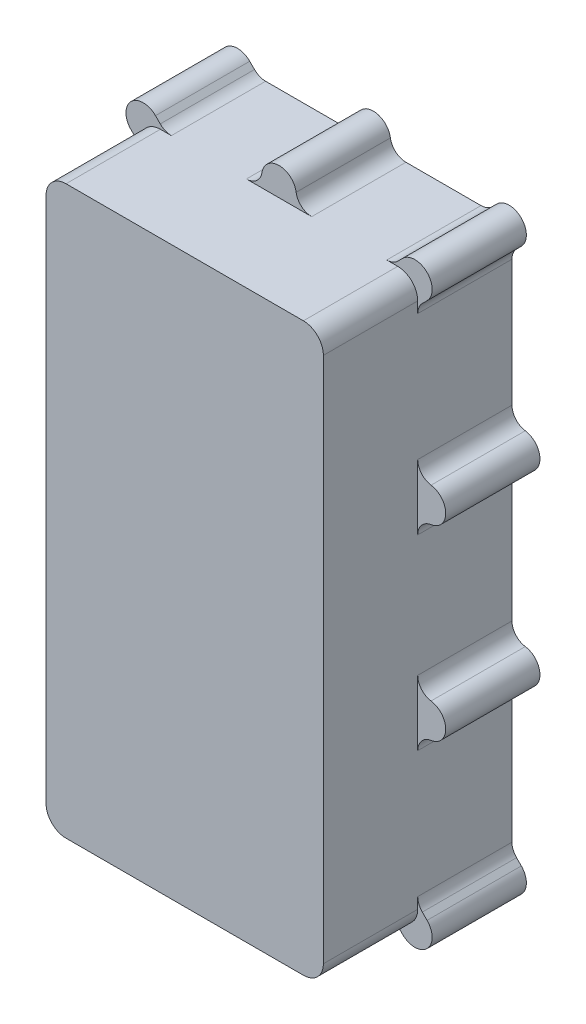
SolidWorks part; units mm, degrees
material "ABS"
ref_plane "X-Y Datum" through (0, 0, 0) normal (0, 0, 1) x (1, 0, 0)
ref_plane "X-Z Datum" through (0, 0, 0) normal (0, 1, 0) x (1, 0, 0)
ref_plane "Y-Z Datum" through (0, 0, 0) normal (1, 0, 0) x (0, 0, -1)
sketch "Sketch1" plane through (0, 0, 0) normal (0, 0, 1) x (1, 0, 0)
  line L0 (1.8162, 48.1563) -> (125.4513, 48.1563) construction
  line L1 (24.3593, 48.1563) -> (24.3593, 120.2923) construction
  line L3 (24.3593, 120.2923) -> (125.4513, 120.2923) construction
  line L8 (125.4513, 48.1563) -> (125.4513, 120.2923) construction
  line L33 (24.3593, 120.2923) -> (1.8162, 120.2923) construction
  line L34 (24.3593, 120.2923) -> (24.3593, 48.1563) construction
  line L35 (63.6337, 48.1563) -> (63.6337, 43.0763) construction
  line L36 (1.8162, 120.2923) -> (1.8162, 48.1563) construction
  line L41 (24.3593, 120.2923) -> (23.7243, 120.2923) construction
  line L42 (24.3593, 120.2923) -> (24.3593, 122.8323) construction
  line L44 (27.5343, 14.7553) -> (27.5343, 43.0763) construction
  line L45 (125.4513, 120.2923) -> (127.9913, 120.2923) construction
  line L46 (27.5343, 14.7553) -> (125.4513, 14.7553) construction
  line L47 (23.7243, 122.8323) -> (127.9913, 122.8323)
  line L48 (23.7243, 122.8323) -> (23.7243, -21.9477)
  line L49 (23.7243, -21.9477) -> (127.9913, -21.9477)
  line L50 (127.9913, 122.8323) -> (127.9913, -21.9477)
  line L51 (125.4513, 14.7553) -> (125.4513, 43.0763) construction
  line L52 (27.5343, 43.0763) -> (125.4513, 43.0763) construction
  line L53 (23.7243, 120.2923) -> (23.7243, 48.1563) construction
  circle A17 centre (30.4553, 114.1963) radius 2.1 construction
  circle A18 centre (119.8633, 115.2123) radius 2.1 construction
  circle A19 centre (119.6813, 54.2533) radius 2.1 construction
  circle A20 centre (29.4393, 53.2363) radius 2.1 construction
  circle A26 centre (31.9793, 18.4383) radius 2.1 construction
  circle A27 centre (31.9793, 39.3933) radius 2.1 construction
  circle A28 centre (120.6193, 28.8183) radius 2.1 construction
sketch "Sketch2" plane through (0, 0, 0) normal (0, 0, 1) x (1, 0, 0)
  line L4 (55.176, 122.8323) -> (127.9913, 122.8323)
  line L6 (55.176, 48.5244) -> (55.176, 50.9244) construction
  line L7 (55.176, -21.05) -> (127.9913, -21.05)
  line L8 (127.9913, 122.8323) -> (127.9913, -21.05)
  line L9 (55.176, 110.2103) -> (127.9913, -21.05) construction
  line L10 (55.176, -8.428) -> (127.9913, 122.8323) construction
  line L11 (55.176, 50.9244) -> (55.176, -21.05)
  line L12 (55.176, 50.9244) -> (55.176, 122.8323)
  circle A7 centre (88.0827, 6.45) radius 27.5
  circle A8 centre (88.0294, 95.3501) radius 27.5
  circle A9 centre (98.216, 50.8911) radius 6.477
  circle A10 centre (77.896, 50.9089) radius 6.477
  circle A11 centre (121.5143, 31.8208) radius 6.477
  circle A12 centre (115.996, 50.8756) radius 2.4
  circle A13 centre (55.176, 50.9244) radius 2.4
  point P14 (88.0827, 50.8911)
sketch "Sketch3" plane through (0, 0, 0) normal (0, 0, 1) x (1, 0, 0)
  line L7 (0, 0) -> (76.2, 0)
  line L10 (0, 0) -> (0, 168.275)
  line L11 (0, 168.275) -> (76.2, 168.275)
  line L12 (76.2, 0) -> (76.2, 168.275)
  dimension "D1" = 168.275
  dimension "D2" = 76.2
extrude "Boss-Extrude1" add sketch "Sketch3" along normal blind 53.975
shell "Shell1" thickness 6 removed face at (38.1, 84.1375, 0) outward yes
fillet "Fillet1" radius 5.334 4 edges at (76.2, 168.275, 26.9875) (76.2, 0, 26.9875) (0, 0, 26.9875) (0, 168.275, 26.9875)
fillet "Fillet2" radius 6.35 4 edges at (-6, -6, 29.9875) (-6, 174.275, 29.9875) (82.2, 174.275, 29.9875) (82.2, -6, 29.9875)
sketch "Sketch6" plane through (0, 0, 0) normal (0, 0, -1) x (-1, 0, 0)
  line L8 (-5.334, 172.5577) -> (-70.866, 172.5577)
  line L9 (-80.4827, 162.941) -> (-80.4827, 5.334)
  line L10 (-70.866, -4.2827) -> (-5.334, -4.2827)
  line L11 (4.2827, 5.334) -> (4.2827, 162.941)
  line L12 (-79.2, 162.941) -> (-79.2, 5.334)
  line L13 (-70.866, -3) -> (-5.334, -3)
  line L14 (3, 5.334) -> (3, 162.941)
  line L15 (-5.334, 171.275) -> (-70.866, 171.275)
  line L16 (-79.2, 162.941) -> (-79.2, 5.334) construction
  line L17 (-70.866, -3) -> (-5.334, -3) construction
  line L18 (3, 5.334) -> (3, 162.941) construction
  line L19 (-5.334, 171.275) -> (-70.866, 171.275) construction
  line L20 (-77.9173, 162.941) -> (-77.9173, 5.334)
  line L21 (-70.866, -1.7173) -> (-5.334, -1.7173)
  line L22 (1.7173, 5.334) -> (1.7173, 162.941)
  line L23 (-5.334, 169.9923) -> (-70.866, 169.9923)
  arc A8 (-70.866, 172.5577) -> (-80.4827, 162.941) centre (-70.866, 162.941) ccw
  arc A9 (-80.4827, 5.334) -> (-70.866, -4.2827) centre (-70.866, 5.334) ccw
  arc A10 (-5.334, -4.2827) -> (4.2827, 5.334) centre (-5.334, 5.334) ccw
  arc A11 (4.2827, 162.941) -> (-5.334, 172.5577) centre (-5.334, 162.941) ccw
  arc A12 (-70.866, 171.275) -> (-79.2, 162.941) centre (-70.866, 162.941) ccw
  arc A13 (-79.2, 5.334) -> (-70.866, -3) centre (-70.866, 5.334) ccw
  arc A14 (-5.334, -3) -> (3, 5.334) centre (-5.334, 5.334) ccw
  arc A15 (3, 162.941) -> (-5.334, 171.275) centre (-5.334, 162.941) ccw
  arc A16 (-70.866, 171.275) -> (-79.2, 162.941) centre (-70.866, 162.941) ccw construction
  arc A17 (-79.2, 5.334) -> (-70.866, -3) centre (-70.866, 5.334) ccw construction
  arc A18 (-5.334, -3) -> (3, 5.334) centre (-5.334, 5.334) ccw construction
  arc A19 (3, 162.941) -> (-5.334, 171.275) centre (-5.334, 162.941) ccw construction
  arc A20 (-77.9173, 5.334) -> (-70.866, -1.7173) centre (-70.866, 5.334) ccw
  arc A21 (-5.334, -1.7173) -> (1.7173, 5.334) centre (-5.334, 5.334) ccw
  arc A22 (1.7173, 162.941) -> (-5.334, 169.9923) centre (-5.334, 162.941) ccw
  arc A23 (-70.866, 169.9923) -> (-77.9173, 162.941) centre (-70.866, 162.941) ccw
  dimension "D4" = 7.0513
  dimension "D5" = 2.5654
  dimension "D1" = 3
  dimension "D2" = 1.2827
  dimension "D3" = 1.2827
extrude "Cut-Extrude1" cut sketch "Sketch6" against normal blind 1.2446
fillet "Fillet3" radius 0.254 16 edges at (-4.2827, 84.1375, 1.2446) (-1.466, -1.466, 1.2446) (38.1, -4.2827, 1.2446) (77.666, -1.466, 1.2446) (80.4827, 84.1375, 1.2446) (77.666, 169.741, 1.2446) (38.1, 172.5577, 1.2446) (-1.466, 169.741, 1.2446) (75.852, 167.927, 1.2446) (77.9173, 84.1375, 1.2446) (75.852, 0.348, 1.2446) (38.1, -1.7173, 1.2446) (0.348, 0.348, 1.2446) (-1.7173, 84.1375, 1.2446) (0.348, 167.927, 1.2446) (38.1, 169.9923, 1.2446)
fillet "Fillet4" radius 0.127 16 edges at (75.852, 167.927, 0) (38.1, 169.9923, 0) (0.348, 167.927, 0) (-1.7173, 84.1375, 0) (0.348, 0.348, 0) (38.1, -1.7173, 0) (75.852, 0.348, 0) (77.666, 169.741, 0) (38.1, 172.5577, 0) (-1.466, 169.741, 0) (-4.2827, 84.1375, 0) (-1.466, -1.466, 0) (38.1, -4.2827, 0) (77.666, -1.466, 0) (77.9173, 84.1375, 0) (80.4827, 84.1375, 0)
sketch "Sketch7" plane through (0, 0, 53.975) normal (0, 0, -1) x (-1, 0, 0)
  line L0 (-76.2, 32) -> (0, 32)
  line L1 (-76.2, 5.334) -> (-76.2, 162.941) construction
  line L2 (0, 162.941) -> (0, 5.334) construction
  line L3 (-76.2, 34.5) -> (0, 34.5)
  line L4 (-5.334, 0) -> (-70.866, 0) construction
  line L5 (-76.2, 32) -> (-76.2, 34.5)
  line L6 (0, 32) -> (0, 34.5)
  dimension "D2" = 32
  dimension "D1" = 2.5
extrude "Boss-Extrude2" add sketch "Sketch7" along normal up to surface (53.975 mm away) up to face at (38.1, 84.1375, 0)
sketch "Sketch8" plane through (0, 0, 0) normal (0, 0, -1) x (-1, 0, 0)
  line L0 (-5.334, 5.334) -> (5.0914, -5.0914)
  line L1 (-1.7782, -6) -> (1.2023, -8.9805)
  line L2 (-0.35, -6) -> (-75.85, -6) construction
  line L3 (-5.334, -4.2827) -> (-5.334, -4.4097)
  line L4 (4.4097, 5.334) -> (4.2827, 5.334)
  line L5 (-5.334, -4.2827) -> (-5.334, -4.4097)
  line L6 (4.4097, 5.334) -> (4.2827, 5.334)
  line L7 (6, 1.7782) -> (8.9805, -1.2023)
  line L8 (6, 167.925) -> (6, 0.35) construction
  line L9 (-38.1, -6) -> (-38.1, 174.275) construction
  line L10 (-75.85, 174.275) -> (-0.35, 174.275) construction
  line L11 (-82.2, 84.1375) -> (6, 84.1375) construction
  line L12 (-82.2, 0.35) -> (-82.2, 167.925) construction
  circle A0 centre (5.0914, -5.0914) radius 3.025
  circle A1 centre (5.0914, -5.0914) radius 5.5
  arc A3 (-5.334, -4.4097) -> (4.4097, 5.334) centre (-5.334, 5.334) ccw
  arc A4 (-5.334, -4.2827) -> (4.2827, 5.334) centre (-5.334, 5.334) ccw
  arc A5 (-5.334, -4.4097) -> (4.4097, 5.334) centre (-5.334, 5.334) ccw
  arc A6 (-5.334, -4.2827) -> (4.2827, 5.334) centre (-5.334, 5.334) ccw
  point P6 (1.5558, -1.5558)
  dimension "D1" = 6.05
  dimension "D4" = 11
  dimension "D3" = 5
  dimension "D2" = 0
extrude "Boss-Extrude3" add sketch "Sketch8" against normal blind 29.972
sketch "Sketch9" plane through (0, 0, 0) normal (0, 0, -1) x (-1, 0, 0)
  circle A0 centre (5.0914, -5.0914) radius 3.025 construction
  circle A1 centre (5.0914, -5.0914) radius 3.025
  dimension "D1" = 6.05
extrude "Cut-Extrude2" cut sketch "Sketch9" against normal blind 9
ref_plane "Plane1" through (38.1, 0, 0) normal (-1, 0, 0) x (0, 0, 1)
ref_plane "Plane2" through (0, 84.1375, 0) normal (0, -1, 0) x (-1, 0, 0)
mirror "Mirror1" about plane through (38.1, 0, 0) normal (-1, 0, 0) of "Cut-Extrude2", "Boss-Extrude3"
mirror "Mirror2" about plane through (0, 84.1375, 0) normal (0, -1, 0) of "Cut-Extrude2", "Boss-Extrude3", "Mirror1"
sketch "Sketch10" plane through (0, 0, 0) normal (0, 0, -1) x (-1, 0, 0)
  line L0 (6, 84.1375) -> (39.3327, 84.1375) construction
  line L2 (6, 166.4968) -> (6, 1.7782) construction
  line L3 (6, 84.1375) -> (6, 157.4914)
  line L4 (6, 113.8555) -> (9.4097, 113.8555) construction
  line L5 (4.4097, 162.941) -> (4.4097, 5.334) construction
  line L7 (9.4097, 119.3555) -> (6, 119.3555)
  line L9 (9.4097, 108.3555) -> (6, 108.3555)
  line L10 (9.4097, 48.9195) -> (6, 48.9195)
  line L11 (9.4097, 59.9195) -> (6, 59.9195)
  circle A4 centre (9.4097, 113.8555) radius 3.025
  circle A5 centre (9.4097, 113.8555) radius 5.5
  circle A6 centre (9.4097, 54.4195) radius 3.025
  circle A7 centre (9.4097, 54.4195) radius 5.5
  point P0 (5.0914, 173.3664)
  point P1 (5.0914, -5.0914)
  point P3 (-81.2914, -5.0914)
  dimension "D3" = 89.2289
  dimension "D4" = 6.05
  dimension "D5" = 11
  dimension "D1" = 178.4577
  dimension "D2" = 86.3827
  dimension "D6" = 5
  dimension "D7" = 29.718
  dimension "D8" = 59.5109
  dimension "D9" = 59.436
  dimension "D10" = 59.5109
extrude "Boss-Extrude4" add sketch "Sketch10" against normal blind 29.972
sketch "Sketch11" plane through (0, 0, 0) normal (0, 0, -1) x (-1, 0, 0)
  circle A0 centre (9.4097, 54.4195) radius 3.025 construction
  circle A1 centre (9.4097, 113.8555) radius 3.025 construction
  circle A2 centre (9.4097, 54.4195) radius 3.025
  circle A3 centre (9.4097, 113.8555) radius 3.025
  dimension "D1" = 6.05
extrude "Cut-Extrude3" cut sketch "Sketch11" against normal blind 9
mirror "Mirror3" about plane through (38.1, 0, 0) normal (-1, 0, 0) of "Cut-Extrude3", "Boss-Extrude4"
sketch "Sketch12" plane through (0, 0, 0) normal (0, 0, -1) x (-1, 0, 0)
  line L0 (-74.4218, -6) -> (-1.7782, -6)
  line L1 (-38.1, -6) -> (-38.1, -9.4097) construction
  line L2 (-5.334, -4.4097) -> (-70.866, -4.4097) construction
  line L3 (-43.6, -9.4097) -> (-43.6, -6)
  line L4 (-32.6, -9.4097) -> (-32.6, -6)
  circle A0 centre (-38.1, -9.4097) radius 3.025
  circle A1 centre (-38.1, -9.4097) radius 5.5
  point P15 (-81.2914, -5.0914)
  point P16 (5.0914, -5.0914)
  dimension "D2" = 6.05
  dimension "D4" = 11
  dimension "D1" = 43.1914
  dimension "D3" = 5
  dimension "D5" = 86.3827
extrude "Boss-Extrude5" add sketch "Sketch12" against normal blind 29.972
sketch "Sketch13" plane through (0, 0, 0) normal (0, 0, -1) x (-1, 0, 0)
  circle A0 centre (-38.1, -9.4097) radius 3.025 construction
  circle A1 centre (-38.1, -9.4097) radius 3.025
extrude "Cut-Extrude4" cut sketch "Sketch13" against normal blind 9
mirror "Mirror4" about plane through (0, 84.1375, 0) normal (0, -1, 0) of "Cut-Extrude4", "Boss-Extrude5"
sketch "Sketch17" plane through (-6, 0, 0) normal (-1, 0, 0) x (0, 0, 1)
  line L0 (59.975, 167.925) -> (59.975, 0.35) construction
  line L1 (0, 34.5) -> (53.975, 34.5) construction
  line L2 (53.975, 32) -> (53.975, 5.334) construction
  circle A0 centre (38.385, 85.3) radius 9.525
  circle A1 centre (38.385, 85.3) radius 14.2875
  circle A2 centre (38.385, 18.667) radius 6.35
  circle A3 centre (38.385, 18.667) radius 10.795
  point P10 (53.975, 18.667)
  dimension "D1" = 19.05
  dimension "D4" = 28.575
  dimension "D5" = 12.7
  dimension "D6" = 21.59
  dimension "D2" = 21.59
  dimension "D3" = 50.8
extrude "Cut-Extrude6" cut sketch "Sketch17" against normal blind 6 contours A0 | A2
sketch "Sketch18" plane through (0, 0, 0) normal (1, 0, 0) x (0, 0, -1)
  circle A0 centre (-38.385, 85.3) radius 14.2875 construction
  circle A1 centre (-38.385, 85.3) radius 14.2875
  circle A2 centre (-38.385, 18.667) radius 10.795 construction
  circle A3 centre (-38.385, 18.667) radius 10.795
extrude "Cut-Extrude7" cut sketch "Sketch18" against normal blind 3
fillet "Fillet5" radius 5 20 edges at (1.7782, -6, 14.986) (-6, 1.7782, 14.986) (32.6, -6, 14.986) (43.6, -6, 14.986) (74.4218, -6, 14.986) (82.2, 1.7782, 14.986) (82.2, 48.9195, 14.986) (82.2, 59.9195, 14.986) (82.2, 108.3555, 14.986) (82.2, 119.3555, 14.986) (82.2, 166.4968, 14.986) (74.4218, 174.275, 14.986) (43.6, 174.275, 14.986) (32.6, 174.275, 14.986) (1.7782, 174.275, 14.986) (-6, 166.4968, 14.986) (-6, 108.3555, 14.986) (-6, 119.3555, 14.986) (-6, 59.9195, 14.986) (-6, 48.9195, 14.986)
